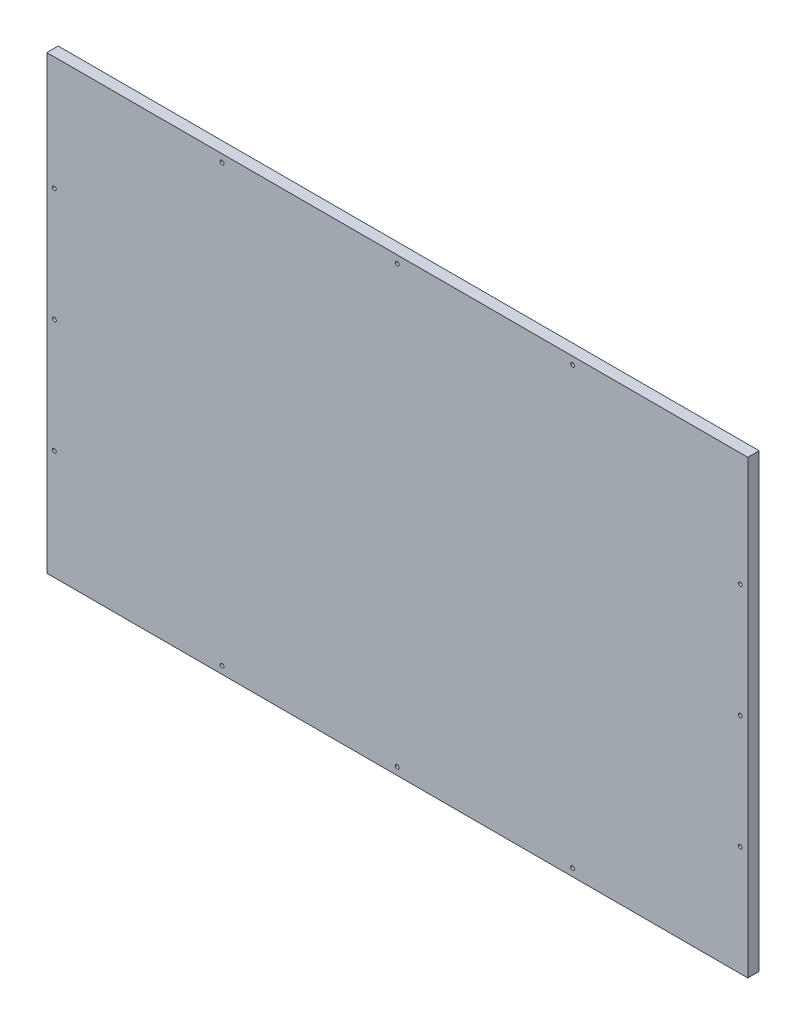
SolidWorks part; units mm, degrees
material "西洋杉"
ref_plane "正面" through (0, 0, 0) normal (0, 0, 1) x (1, 0, 0)
ref_plane "平面" through (0, 0, 0) normal (0, 1, 0) x (1, 0, 0)
ref_plane "右側面" through (0, 0, 0) normal (1, 0, 0) x (0, 0, -1)
sketch "ｽｹｯﾁ1" plane through (0, 0, 0) normal (0, 0, 1) x (1, 0, 0)
  line L1 (-462.5, 297.5) -> (462.5, 297.5)
  line L2 (-462.5, 297.5) -> (-462.5, -297.5)
  line L3 (-462.5, -297.5) -> (462.5, -297.5)
  line L4 (462.5, 297.5) -> (462.5, -297.5)
  line L5 (-462.5, 297.5) -> (462.5, -297.5) construction
  line L6 (-462.5, -297.5) -> (462.5, 297.5) construction
  point P0 (0, 0)
  dimension "D1" = 595
  dimension "D2" = 925
extrude "ﾎﾞｽ - 押し出し1" add sketch "ｽｹｯﾁ1" along normal blind 15
sketch "ｽｹｯﾁ2" plane through (0, 0, 15) normal (0, 0, 1) x (1, 0, 0)
  line L0 (-452.5, 297.5) -> (-452.5, -297.5) construction
  line L1 (462.5, 297.5) -> (-462.5, 297.5) construction
  line L2 (-462.5, -297.5) -> (462.5, -297.5) construction
  line L3 (-462.5, 297.5) -> (-462.5, -297.5) construction
  line L4 (-462.5, 287.5) -> (462.5, 287.5) construction
  line L5 (462.5, -297.5) -> (462.5, 297.5) construction
  circle A0 centre (-452.5, 147.5) radius 2.5
  circle A1 centre (-452.5, -2.5) radius 2.5
  circle A2 centre (-452.5, -152.5) radius 2.5
  circle A3 centre (-231.25, 287.5) radius 2.5
  circle A4 centre (0, 287.5) radius 2.5
  circle A5 centre (231.25, 287.5) radius 2.5
  dimension "D2" = 5
  dimension "D7" = 5
  dimension "D1" = 10
  dimension "D3" = 150
  dimension "D5" = 10
  dimension "D6" = 925
  dimension "D8" = 231.25
  dimension "D10" = 595
  dimension "D11" = 150
  dimension "D4" = 3
  dimension "D9" = 3
extrude "ｶｯﾄ - 押し出し1" cut sketch "ｽｹｯﾁ2" against normal through all contours A3 | A4 | A5
extrude "ｶｯﾄ - 押し出し2" cut sketch "ｽｹｯﾁ2<3>" against normal through all contours A0 | A1 | A2
sketch "ｽｹｯﾁ2<3>" plane through (0, 0, 15) normal (0, 0, 1) x (1, 0, 0) same geometry as "ｽｹｯﾁ2"
mirror "ﾐﾗｰ1" about plane through (0, 0, 0) normal (0, 1, 0) of "ｶｯﾄ - 押し出し1"
mirror "ﾐﾗｰ2" about plane through (0, 0, 0) normal (1, 0, 0) of "ｶｯﾄ - 押し出し2"
equation "\"D8@ｽｹｯﾁ2\"=\"D6@ｽｹｯﾁ2\"/4"
